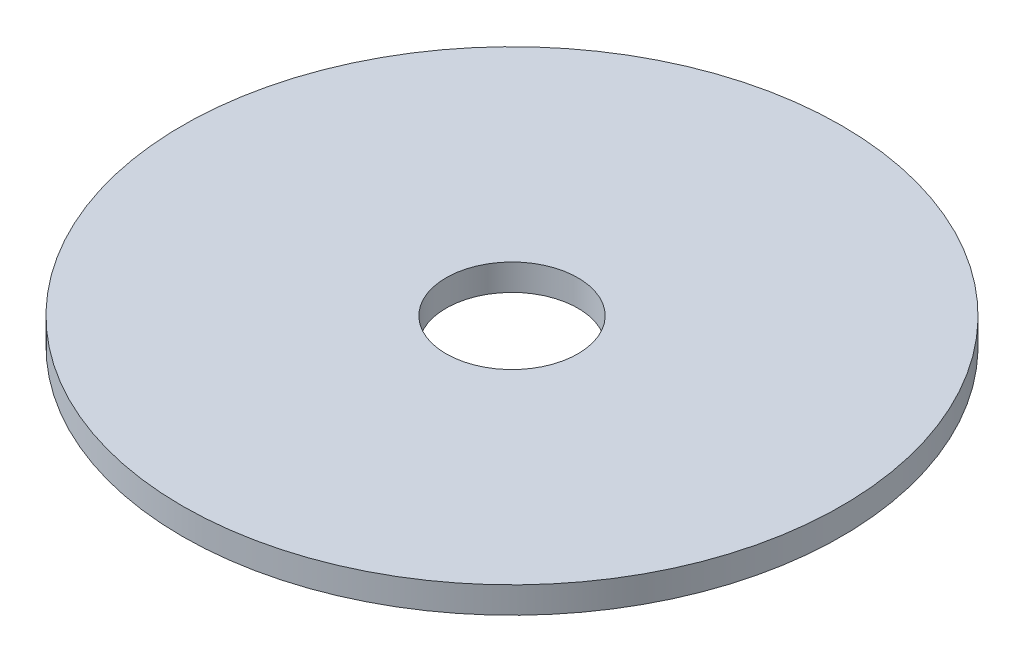
SolidWorks part; units mm, degrees
material "AISI 304"
ref_plane "前视基准面" through (0, 0, 0) normal (0, 0, 1) x (1, 0, 0)
ref_plane "上视基准面" through (0, 0, 0) normal (0, 1, 0) x (1, 0, 0)
ref_plane "右视基准面" through (0, 0, 0) normal (1, 0, 0) x (0, 0, -1)
sketch "草图1" plane through (0, 0, 0) normal (0, 1, 0) x (1, 0, 0)
  circle A0 centre (0, 0) radius 25
  circle A1 centre (0, 0) radius 5
  dimension "D1" = 50
  dimension "D2" = 10
base flange "基体-法兰1" sketch "草图1" thickness 2 reverse thickness direction no parameters "D1"=2
sketch "折弯-线1" [suppressed] plane through (0, 0, 0) normal (0, 1, 0) x (1, 0, 0)
sketch "边界框1" [suppressed] plane through (0, 0, 0) normal (0, 1, 0) x (1, 0, 0)
sheet metal parameters "钣金1" thickness 2 parameters "D1"=2
flat pattern "平板型式1" [suppressed]
sketch "折弯-线2" plane through (0, 0, 0) normal (0, 1, 0) x (1, 0, 0)
sketch3d "边界框2" [suppressed]
  line L0 (-25.0403, 24.9596, 0) -> (-24.9596, -25.0403, 0) construction
  line L1 (24.9596, 25.0403, 0) -> (25.0403, -24.9596, 0) construction
  line L2 (-25.0403, 24.9596, 0) -> (24.9596, 25.0403, 0) construction
  line L3 (-24.9596, -25.0403, 0) -> (25.0403, -24.9596, 0) construction
